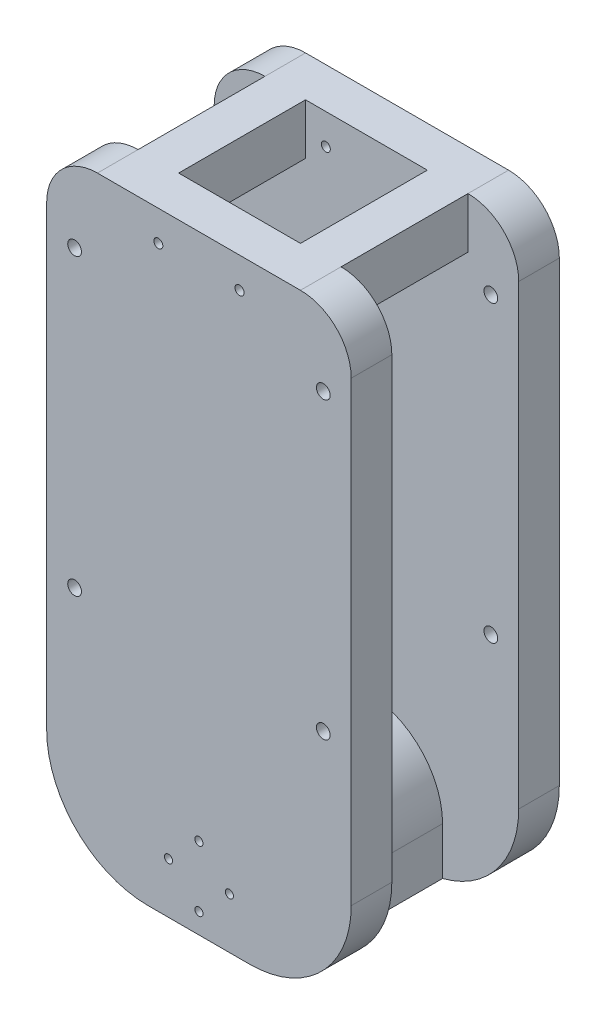
SolidWorks part; units mm, degrees
ref_plane "Front Plane" through (0, 0, 0) normal (0, 0, 1) x (1, 0, 0)
ref_plane "Top Plane" through (0, 0, 0) normal (0, 1, 0) x (1, 0, 0)
ref_plane "Right Plane" through (0, 0, 0) normal (1, 0, 0) x (0, 0, -1)
sketch "Sketch1" plane through (0, 0, 0) normal (0, 0, 1) x (1, 0, 0)
  line L11 (-30, 20.2064) -> (0, 20.2064)
  line L12 (0, 20.2064) -> (30, 20.2064)
  line L13 (30, 20.2064) -> (30, -99.7936)
  line L14 (30, -99.7936) -> (-30, -99.7936)
  line L15 (-30, -99.7936) -> (-30, 20.2064)
  circle A0 centre (-8, 14.2064) radius 0.8836
  circle A1 centre (8, 14.2064) radius 0.8966
  circle A2 centre (0, -89.7936) radius 8 construction
  circle A3 centre (0, -89.7936) radius 6 construction
  circle A4 centre (0, -83.7936) radius 0.8
  circle A5 centre (6, -89.7936) radius 0.8
  circle A6 centre (0, -95.7936) radius 0.8
  circle A7 centre (-6, -89.7936) radius 0.8
  circle A8 centre (-24.5, 5.2064) radius 1.35
  circle A9 centre (24.5, 5.2064) radius 1.35
  circle A10 centre (-24.5, -52.7936) radius 1.35
  circle A11 centre (24.5, -52.7936) radius 1.35
  point P25 (0, -89.7936)
  point P31 (0, 0)
  point P32 (0, 0)
  point P33 (0, 0)
  point P34 (0, 0)
  point P35 (0, 0)
  dimension "D7" = 4
  dimension "D10" = 49
  dimension "D1" = 8
  dimension "D2" = 30
  dimension "D3" = 30
  dimension "D4" = 16
  dimension "D5" = 0
  dimension "D6" = 120
  dimension "D8" = 10
  dimension "D9" = 6
  dimension "D11" = 24.5
  dimension "D12" = 58
  dimension "D13" = 15
extrude "Boss-Extrude1" add sketch "Sketch1" along normal blind 8
sketch "Sketch2" plane through (0, 0, 8) normal (0, 0, 1) x (1, 0, 0)
  line L0 (-12, 20.2064) -> (-12, 10.2064)
  line L1 (30, 20.2064) -> (-30, 20.2064) construction
  line L2 (12, 20.2064) -> (12, 10.2064)
  line L3 (12, 20.2064) -> (20, 20.2064)
  line L4 (20, 20.2064) -> (20, 10.2064)
  line L5 (20, 10.2064) -> (12, 10.2064)
  line L6 (-12, 20.2064) -> (-20, 20.2064)
  line L7 (-20, 20.2064) -> (-20, 10.2064)
  line L8 (-20, 10.2064) -> (-12, 10.2064)
  dimension "D1" = 12
  dimension "D2" = 12
  dimension "D3" = 10
  dimension "D4" = 8
  dimension "D5" = 8
extrude "Boss-Extrude3" add sketch "Sketch2" along normal blind 25
extrude "Boss-Extrude4" add sketch "Sketch1<2>" against normal blind 8 from offset 41
sketch "Sketch1<2>" plane through (0, 0, 0) normal (0, 0, 1) x (1, 0, 0) same geometry as "Sketch1"
sketch "Sketch3" plane through (0, 0, 8) normal (0, 0, 1) x (1, 0, 0)
  line L4 (-30, -99.7936) -> (-10, -99.7936) construction
  line L5 (-6, -89.7936) -> (6, -89.7936) construction
  line L6 (-10, -89.7936) -> (-10, -99.7936)
  line L7 (0, -83.7936) -> (0, -95.7936) construction
  line L8 (10, -89.7936) -> (10, -99.7936)
  line L9 (10, -99.7936) -> (30, -99.7936) construction
  line L10 (-10, -99.7936) -> (10, -99.7936)
  arc A1 (10, -89.7936) -> (-10, -89.7936) centre (0, -89.7936) ccw
extrude "Cut-Extrude1" cut sketch "Sketch3" against normal blind 3
extrude "Cut-Extrude2" cut sketch "Sketch3<2>" along normal blind 3 from surface starting at face at (25.85, -52.7936, 33)
sketch "Sketch3<2>" plane through (0, 0, 8) normal (0, 0, 1) x (1, 0, 0) same geometry as "Sketch3"
sketch "Sketch4" plane through (0, 0, 33) normal (0, 0, -1) x (-1, 0, 0)
  line L0 (-15, -89.7936) -> (-15, -99.7936)
  line L1 (15, -89.7936) -> (15, -99.7936)
  line L2 (-10, -89.7936) -> (-10, -99.7936)
  line L3 (15, -99.7936) -> (30, -99.7936)
  line L4 (-15, -99.7936) -> (-10, -99.7936)
  line L5 (10, -89.7936) -> (10, -99.7936)
  line L6 (-15, -99.7936) -> (-10, -99.7936)
  line L7 (10, -99.7936) -> (15, -99.7936)
  line L8 (15, -99.7936) -> (10, -99.7936)
  line L10 (-15, -99.7936) -> (-10, -99.7936)
  line L11 (10, -99.7936) -> (15, -99.7936)
  line L15 (-30, -99.7936) -> (-10, -99.7936)
  line L16 (-10, -99.7936) -> (-10, -89.7936)
  line L17 (10, -89.7936) -> (10, -99.7936)
  line L18 (10, -99.7936) -> (30, -99.7936)
  line L19 (30, -99.7936) -> (30, 20.2064)
  line L20 (30, 20.2064) -> (20, 20.2064)
  line L21 (20, 20.2064) -> (20, 10.2064)
  line L22 (20, 10.2064) -> (12, 10.2064)
  line L23 (12, 10.2064) -> (12, 20.2064)
  line L24 (12, 20.2064) -> (-12, 20.2064)
  line L25 (-12, 20.2064) -> (-12, 10.2064)
  line L26 (-12, 10.2064) -> (-20, 10.2064)
  line L27 (-20, 10.2064) -> (-20, 20.2064)
  line L28 (-20, 20.2064) -> (-30, 20.2064)
  line L29 (-30, 20.2064) -> (-30, -99.7936)
  line L30 (-30, -99.7936) -> (-15, -99.7936)
  line L34 (30, -99.7936) -> (30, 20.2064)
  line L35 (30, 20.2064) -> (20, 20.2064)
  line L36 (20, 20.2064) -> (20, 10.2064)
  line L37 (20, 10.2064) -> (12, 10.2064)
  line L38 (12, 10.2064) -> (12, 20.2064)
  line L39 (12, 20.2064) -> (-12, 20.2064)
  line L40 (-12, 20.2064) -> (-12, 10.2064)
  line L41 (-12, 10.2064) -> (-20, 10.2064)
  line L42 (-20, 10.2064) -> (-20, 20.2064)
  line L43 (-20, 20.2064) -> (-30, 20.2064)
  line L44 (-30, 20.2064) -> (-30, -99.7936)
  arc A0 (15, -89.7936) -> (-15, -89.7936) centre (0, -89.7936) ccw
  arc A1 (10, -89.7936) -> (-10, -89.7936) centre (0, -89.7936) ccw
  arc A2 (10, -89.7936) -> (-10, -89.7936) centre (0, -89.7936) ccw
  arc A3 (10, -89.7936) -> (-10, -89.7936) centre (0, -89.7936) ccw
  arc A4 (-10, -89.7936) -> (10, -89.7936) centre (0, -89.7936) cw
  dimension "D1" = 0
sketch "Sketch5" plane through (0, 0, 33) normal (0, 0, -1) x (-1, 0, 0)
  line L0 (-15, -89.7936) -> (-15, -99.7936)
  line L1 (-15, -99.7936) -> (-10, -99.7936)
  line L2 (-10, -99.7936) -> (-10, -89.7936)
  line L3 (10, -89.7936) -> (10, -99.7936)
  line L4 (10, -99.7936) -> (15, -99.7936)
  line L5 (15, -99.7936) -> (15, -89.7936)
  arc A0 (10, -89.7936) -> (-10, -89.7936) centre (0, -89.7936) ccw
  arc A1 (15, -89.7936) -> (-15, -89.7936) centre (0, -89.7936) ccw
extrude "Boss-Extrude5" add sketch "Sketch5" along normal blind 25
fillet "Fillet1" radius 10 4 edges at (30, 20.2064, 37) (30, 20.2064, 4) (-30, 20.2064, 4) (-30, 20.2064, 37)
fillet "Fillet2" radius 20 2 edges at (-30, -99.7936, 4) (30, -99.7936, 37)
